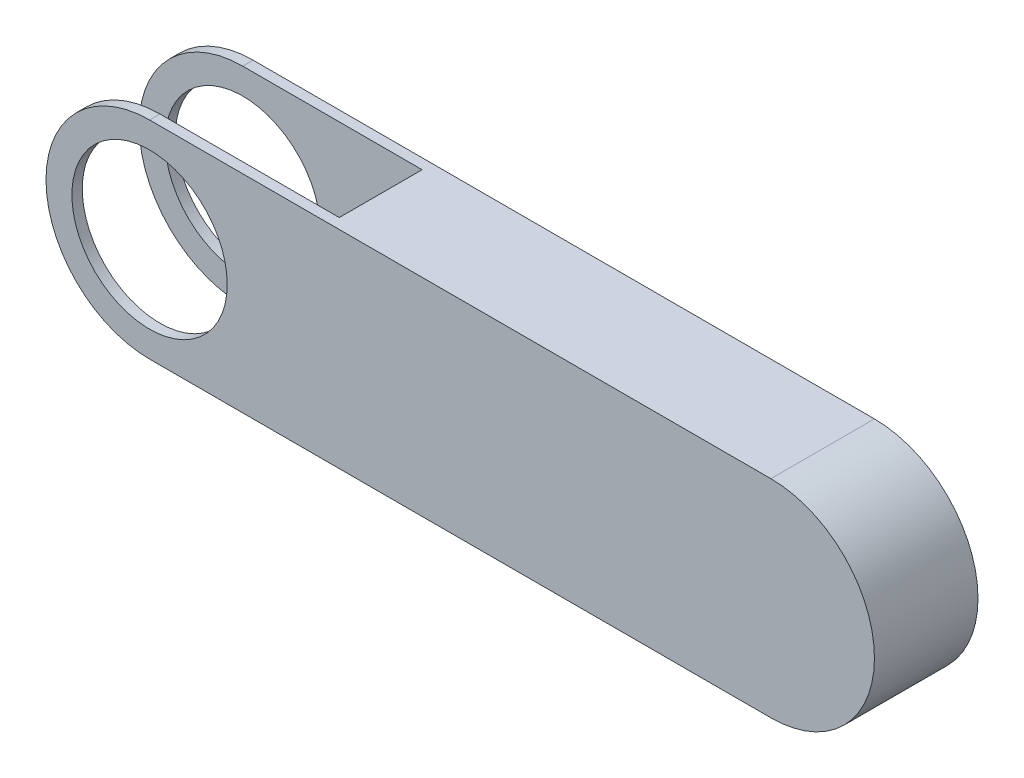
SolidWorks part; units mm, degrees
ref_plane "Front Plane" through (0, 0, 0) normal (0, 0, 1) x (1, 0, 0)
ref_plane "Top Plane" through (0, 0, 0) normal (0, 1, 0) x (1, 0, 0)
ref_plane "Right Plane" through (0, 0, 0) normal (1, 0, 0) x (0, 0, -1)
sketch "Sketch2" plane through (0, 0, 0) normal (0, 0, 1) x (1, 0, 0)
  line L0 (0, 100) -> (600, 100)
  line L1 (0, -100) -> (600, -100)
  circle A0 centre (0, 0) radius 100
  circle A1 centre (600, 0) radius 100
extrude "Boss-Extrude1" add sketch "Sketch2" along normal blind 50 and the other way blind 50 contours A0 | A1 L0 A0 L1 | A1 region at (300, 0, 0) region at (0, 0, 0) region at (600, 0, 0)
sketch "Sketch3" plane through (0, 0, 0) normal (0, 0, 1) x (1, 0, 0)
  circle A0 centre (0, 0) radius 75
extrude "Cut-Extrude1" cut sketch "Sketch3" against normal blind 50 and the other way blind 50
sketch "Sketch4" plane through (0, 0, 0) normal (0, 0, 1) x (1, 0, 0)
  circle A0 centre (0, 0) radius 200
sketch "Sketch5" plane through (0, 0, 50) normal (0, 0, 1) x (1, 0, 0)
extrude "Cut-Extrude2" cut sketch "Sketch4" against normal blind 40 and the other way blind 40
